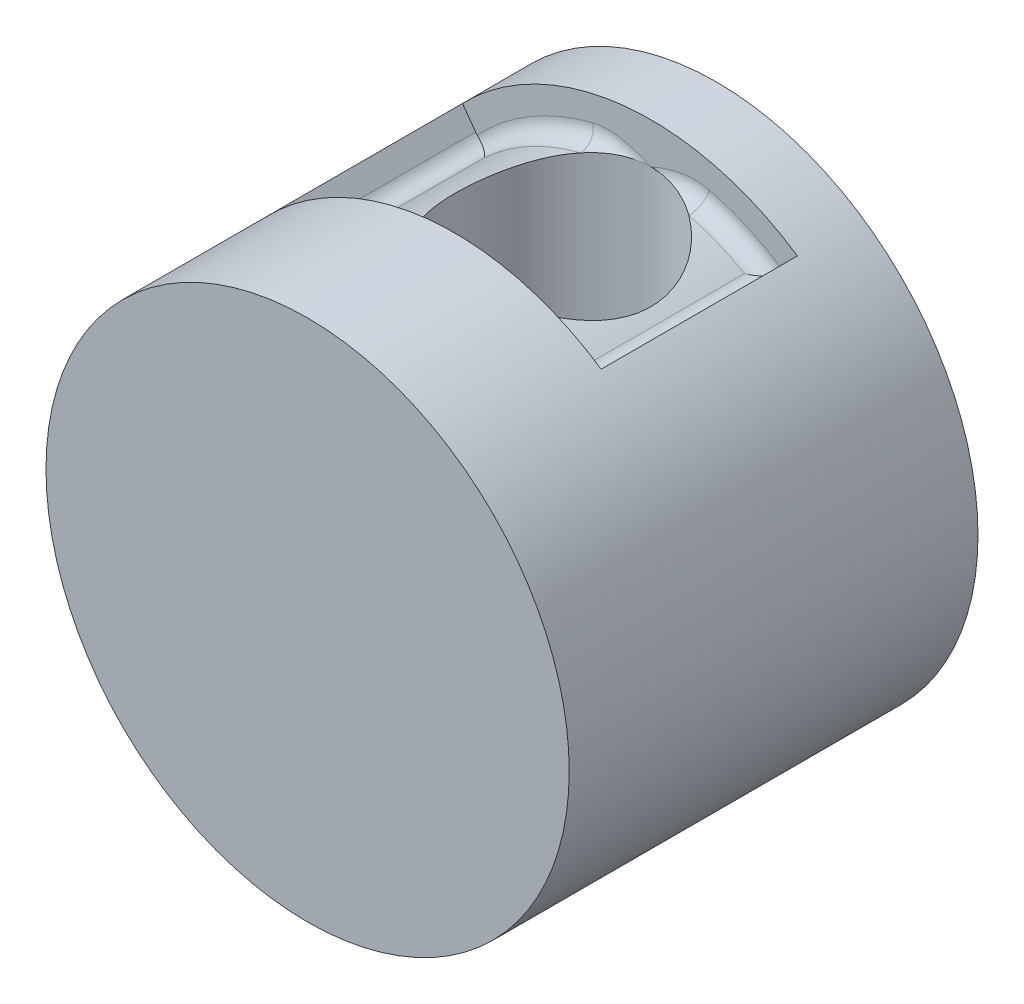
SolidWorks part; units mm, degrees
material "Cobre"
ref_plane "Plano frontal" through (0, 0, 0) normal (0, 0, 1) x (1, 0, 0)
ref_plane "Plano superior" through (0, 0, 0) normal (0, 1, 0) x (1, 0, 0)
ref_plane "Plano direito" through (0, 0, 0) normal (1, 0, 0) x (0, 0, -1)
sketch "Esboço1" plane through (0, 0, 0) normal (0, 0, 1) x (1, 0, 0)
  circle A0 centre (0, 0) radius 16
  dimension "D1" = 32
extrude "Ressalto-extrusão1" add sketch "Esboço1" along normal blind 25
sketch "Esboço2" plane through (0, 0, 0) normal (0, 1, 0) x (1, 0, 0)
  circle A0 centre (0, -10) radius 6
  dimension "D2" = 12
  dimension "D1" = 10
  dimension "D3" = 0
extrude "Corte-extrusão1" cut sketch "Esboço2" against normal through all both and the other way through all
ref_plane "Plano1" through (0, 0, 10) normal (0, 0, -1) x (-1, 0, 0)
sketch "Esboço3" plane through (0, 0, 10) normal (0, 0, -1) x (-1, 0, 0)
  line L0 (-15.1512, 21.7917) -> (-7.4825, 11.2367)
  line L2 (10.0333, 9.0323) -> (19.3036, 21.7917)
  line L3 (19.3036, 21.7917) -> (-15.1512, 21.7917)
  line L4 (0, 0) -> (0, 27.5192) construction
  arc A0 (10.0333, 9.0323) -> (-7.4825, 11.2367) centre (0, 0) ccw
  dimension "D1" = 27
  dimension "D2" = 36
  dimension "D3" = 36
extrude "Corte-extrusão2" cut sketch "Esboço3" against normal blind 6 and the other way blind 6
fillet "Filete1" radius 1 6 edges at (3.9087, 12.9218, 16) (3.9087, 12.9218, 4) (-5.4916, 12.3326, 16) (7.4825, 11.2367, 10) (-10.0333, 9.0323, 10) (-5.4916, 12.3326, 4)
